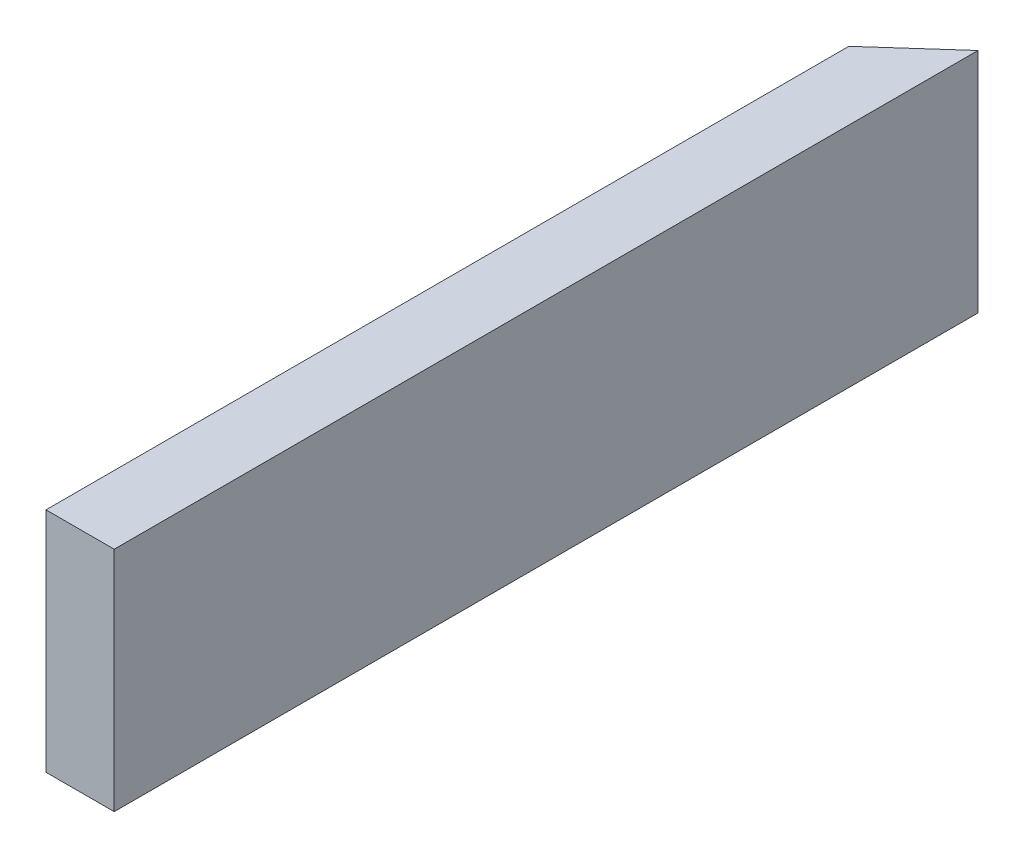
SolidWorks part; units mm, degrees
ref_plane "Front Plane" through (0, 0, 0) normal (0, 0, 1) x (1, 0, 0)
ref_plane "Top Plane" through (0, 0, 0) normal (0, 1, 0) x (1, 0, 0)
ref_plane "Right Plane" through (0, 0, 0) normal (1, 0, 0) x (0, 0, -1)
sketch "Sketch1" plane through (0, 0, 0) normal (0, 0, 1) x (1, 0, 0)
  line L1 (-3.9032, 12.8387) -> (-0.9032, 12.8387)
  line L2 (-3.9032, 12.8387) -> (-3.9032, 2.8387)
  line L3 (-3.9032, 2.8387) -> (-0.9032, 2.8387)
  line L4 (-0.9032, 12.8387) -> (-0.9032, 2.8387)
  dimension "D1" = 3
  dimension "D2" = 10
extrude "Boss-Extrude1" add sketch "Sketch1" along normal blind 38
ref_plane "Plane1" through (0, 12.8387, 0) normal (0, 1, 0) x (1, 0, 0)
sketch "Sketch3" plane through (0, 12.8387, 0) normal (0, 1, 0) x (1, 0, 0)
  line L0 (-0.9032, 0) -> (-3.9032, -2.6823)
  line L1 (-3.9032, -38) -> (-3.9032, 0) construction
  line L2 (-3.9032, -2.6823) -> (-3.9032, 0)
  line L3 (-3.9032, 0) -> (-0.9032, 0)
  dimension "D1" = 41.8
extrude "Cut-Extrude1" cut sketch "Sketch3" against normal blind 52
